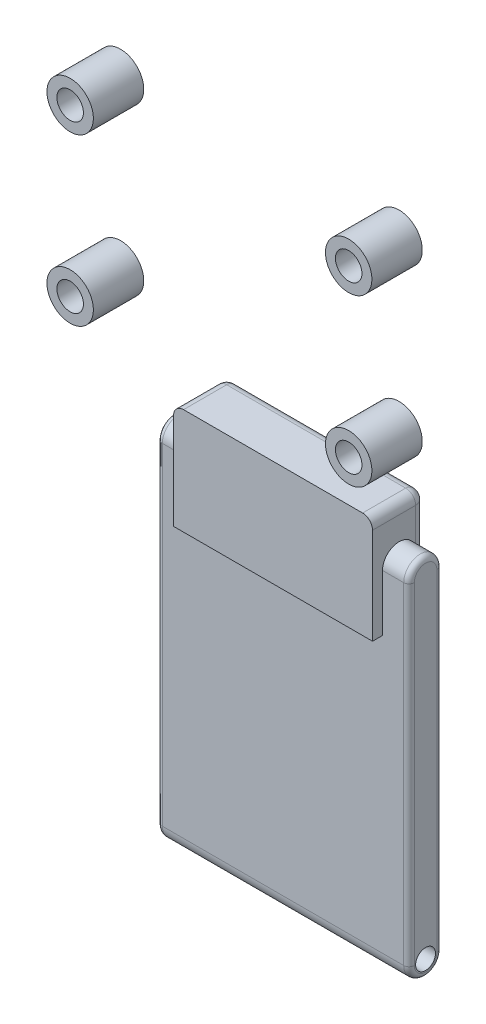
SolidWorks part; units mm, degrees
material "ABS"
ref_plane "Plan de face" through (0, 0, 0) normal (0, 0, 1) x (1, 0, 0)
ref_plane "Plan de dessus" through (0, 0, 0) normal (0, 1, 0) x (1, 0, 0)
ref_plane "Plan de droite" through (0, 0, 0) normal (1, 0, 0) x (0, 0, -1)
ref_plane "Plan1" through (0, -2.78, 0) normal (0, 1, 0) x (-1, 0, 0)
sketch "Esquisse1" plane through (0, -2.78, 0) normal (0, 1, 0) x (-1, 0, 0)
  line L2 (-21.1642, -2.5) -> (-21.1642, -7)
  line L3 (-19.6642, -8.5) -> (0.081, -8.5)
  line L7 (0.081, -7.5) -> (-18.7935, -7.5)
  line L8 (-20.2935, -6) -> (-20.2935, -2.5)
  line L9 (-20.2935, -2.5) -> (-21.1642, -2.5)
  line L11 (0.081, -8.5) -> (0.081, -7.5)
  arc A2 (-21.1642, -7) -> (-19.6642, -8.5) centre (-19.6642, -7) ccw
  arc A3 (-18.7935, -7.5) -> (-20.2935, -6) centre (-18.7935, -6) cw
  dimension "D3" = 1.5
  dimension "D1" = 6
  dimension "D2" = 1
revolve "Révolution1" add sketch "Esquisse1" angle 360 about L0 rebuild error yes
sketch "Esquisse2" plane through (0, 0, -56.3362) normal (0, 0, 1) x (1, 0, 0)
  circle A0 centre (-10.2065, 9.9721) radius 1.75
  circle A1 centre (10.7935, 9.9721) radius 1.75
  circle A2 centre (10.7935, -2.5279) radius 1.75
  circle A3 centre (-10.2065, -2.5279) radius 1.75
  circle A4 centre (-10.2065, 9.9721) radius 1
  circle A5 centre (-10.2065, -2.5279) radius 1
  circle A6 centre (10.7935, -2.5279) radius 1
  circle A7 centre (10.7935, 9.9721) radius 1
  dimension "D1" = 2
  dimension "D2" = 3.5
  dimension "D3" = 2
  dimension "D4" = 3.5
  dimension "D5" = 2
  dimension "D6" = 3.5
  dimension "D7" = 2
  dimension "D8" = 3.5
extrude "Boss.-Extru.1" add sketch "Esquisse2" along normal blind 3.8
sketch "Esquisse3" plane through (0, 0, -57.3362) normal (0, 0, -1) x (-1, 0, 0)
  line L1 (-7.7935, -10.4407) -> (7.2065, -10.4407)
  line L2 (-7.7935, -10.4407) -> (-7.7935, -18.4407)
  line L3 (-7.7935, -18.4407) -> (7.2065, -18.4407)
  line L4 (7.2065, -10.4407) -> (7.2065, -18.4407)
  line L5 (-7.7935, -10.4407) -> (7.2065, -18.4407) construction
  line L6 (-7.7935, -18.4407) -> (7.2065, -10.4407) construction
  circle A0 centre (-0.2935, -14.4407) radius 19.5 construction
  point P0 (-0.2935, -14.4407)
  dimension "D1" = 8
  dimension "D2" = 15
extrude "Boss.-Extru.2" add sketch "Esquisse3" along normal blind 4
fillet "Congé1" radius 0.75 6 edges at (-7.2065, -10.4407, -59.3362) (0.2935, -10.4407, -61.3362) (7.7935, -10.4407, -59.3362) (-7.2065, -14.4407, -61.3362) (0.2935, -18.4407, -61.3362) (7.7935, -14.4407, -61.3362)
sketch "Esquisse4" plane through (7.7935, 0, 0) normal (1, 0, 0) x (0, 0, -1)
  line L0 (60.5862, -18.4407) -> (60.5862, -11.1907) construction
  line L1 (60.5862, -11.1907) -> (57.3362, -11.1907) construction
  line L2 (58.0862, -14.1907) -> (58.0862, -39.1907)
  line L3 (60.5862, -14.1907) -> (60.5862, -39.1907)
  arc A0 (60.5862, -14.1907) -> (58.0862, -14.1907) centre (59.3362, -14.1907) ccw
  arc A1 (58.0862, -39.1907) -> (60.5862, -39.1907) centre (59.3362, -39.1907) ccw
  dimension "D1" = 2.5
  dimension "D2" = 1.25
  dimension "D3" = 3
  dimension "D4" = 25
extrude "Boss.-Extru.3" add sketch "Esquisse4" along normal blind 2
fillet "Congé2" radius 0.4 4 edges at (9.7935, -40.4407, -59.3362) (9.7935, -26.6907, -58.0862) (9.7935, -12.9407, -59.3362) (9.7935, -26.6907, -60.5862)
fillet "Congé5" radius 0.75 1 edges at (7.7935, -18.4407, -59.3362)
sketch "Esquisse5" plane through (7.7935, 0, 0) normal (-1, 0, 0) x (0, 0, 1)
  circle A0 centre (-59.3362, -39.1907) radius 1.25
  arc A1 (-60.5862, -39.1907) -> (-58.0862, -39.1907) centre (-59.3362, -39.1907) ccw construction
  dimension "D1" = 2.5
extrude "Boss.-Extru.4" add sketch "Esquisse5" along normal blind 15
sketch "Esquisse7" plane through (-7.2065, 0, 0) normal (-1, 0, 0) x (0, 0, 1)
  line L0 (-58.0862, -14.1907) -> (-58.0862, -39.1907)
  line L1 (-60.5862, -39.1907) -> (-60.5862, -14.1907)
  arc A0 (-60.5862, -39.1907) -> (-58.0862, -39.1907) centre (-59.3362, -39.1907) ccw
  arc A1 (-58.0862, -14.1907) -> (-60.5862, -14.1907) centre (-59.3362, -14.1907) ccw
  dimension "D2" = 25
extrude "Boss.-Extru.5" add sketch "Esquisse7" along normal blind 2
fillet "Congé6" radius 0.4 4 edges at (-9.2065, -12.9407, -59.3362) (-9.2065, -26.6907, -58.0862) (-9.2065, -40.4407, -59.3362) (-9.2065, -26.6907, -60.5862)
fillet "Congé7" radius 0.75 1 edges at (-7.2065, -18.4407, -59.3362)
extrude "Boss.-Extru.6" add sketch "Esquisse7<2>" against normal blind 15
sketch "Esquisse7<2>" plane through (-7.2065, 0, 0) normal (-1, 0, 0) x (0, 0, 1) same geometry as "Esquisse7"
sketch "Esquisse10" plane through (-9.2065, 0, 0) normal (-1, 0, 0) x (0, 0, 1)
  circle A0 centre (-59.3362, -39.1907) radius 0.75
  dimension "D1" = 1.5
extrude "Enlèv. mat.-Extru.2" cut sketch "Esquisse10" against normal blind 19
